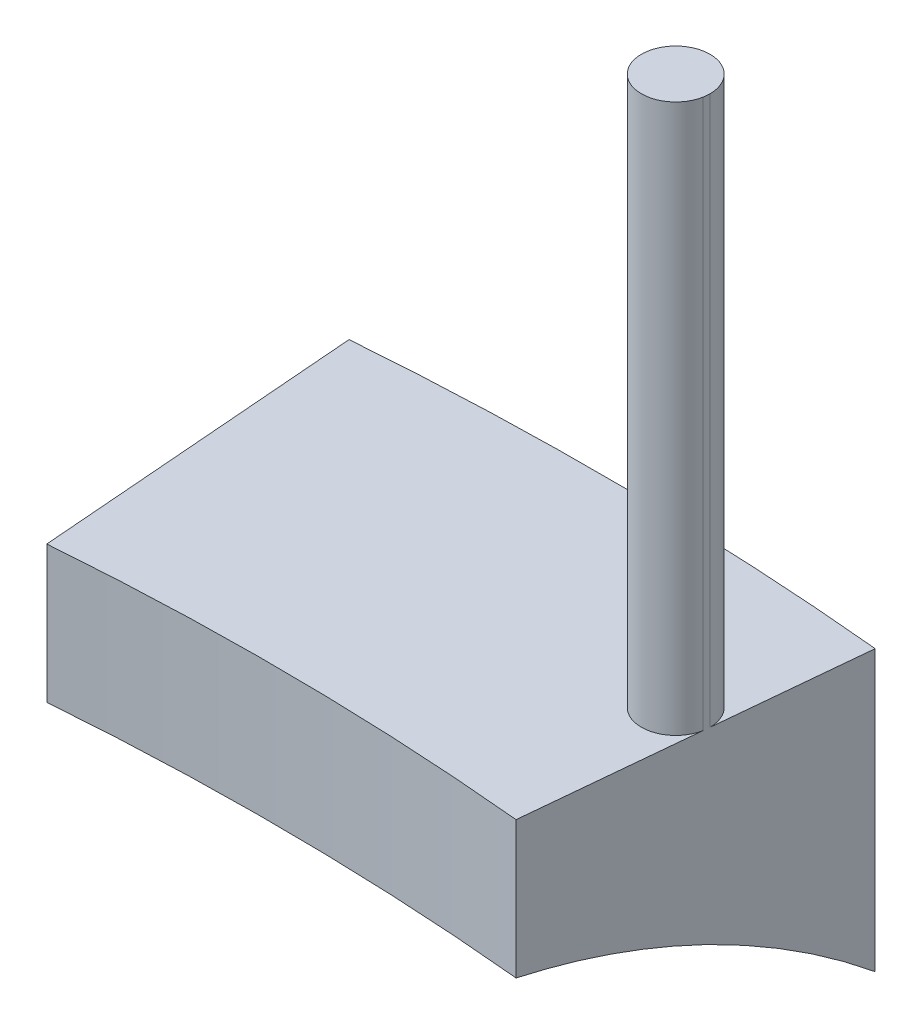
SolidWorks part; units mm, degrees
ref_plane "Front Plane" through (0, 0, 0) normal (0, 0, 1) x (1, 0, 0)
ref_plane "Top Plane" through (0, 0, 0) normal (0, 1, 0) x (1, 0, 0)
ref_plane "Right Plane" through (0, 0, 0) normal (1, 0, 0) x (0, 0, -1)
sketch "Sketch1" plane through (0, 0, 0) normal (0, 1, 0) x (1, 0, 0)
  circle A0 centre (0, 0) radius 140.97
  circle A1 centre (0, 0) radius 125.73
  dimension "D1" = 281.94
  dimension "D2" = 251.46
extrude "Boss-Extrude1" add sketch "Sketch1" along normal blind 12.954
sketch "Sketch3" plane through (0, 12.954, 0) normal (0, 1, 0) x (1, 0, 0)
  line L0 (0, 0) -> (13.4916, 140.3229)
  line L1 (13.4916, 140.3229) -> (0, 0)
  line L2 (0, 0) -> (-11.0802, 140.5339)
  circle A0 centre (0, 0) radius 140.97 construction
  circle A1 centre (0, 0) radius 140.97
  circle M3 centre (0, 0) radius 140.97
  circle M4 centre (0, 0) radius 125.73
  dimension "D1" = 10
extrude "Cut-Extrude1" cut sketch "Sketch3" against normal blind 12.954 contours L0 L2 M4 | L2 L0 M4 M3 region at (-0.0205, 12.954, 2.3917) region at (16.7282, 12.954, -132.3566)
sketch "Sketch5" plane through (0, 0, 0) normal (0, 1, 0) x (1, 0, 0)
  line L0 (-9.8823, 125.341) -> (-11.0802, 140.5339) construction
  line L1 (12.033, 125.1529) -> (13.4916, 140.3229) construction
  arc A1 (-10.4813, 132.9374) -> (12.7623, 132.7379) centre (0, 0) cw
  circle A2 centre (11.2323, 133.3451) radius 1.5875
  dimension "D1" = 3.175
  dimension "D2" = 1.53
  dimension "D3" = 133.35
extrude "Boss-Extrude2" add sketch "Sketch5" along normal blind 38.354 contours A2
sketch "Sketch2" plane through (0, 0, 0) normal (0, 0, 1) x (1, 0, 0)
  line L0 (0, 12.954) -> (-125.73, 12.954)
  line L1 (13.4916, 12.954) -> (-11.0802, 12.954) construction
  line L2 (-125.73, 12.954) -> (-125.73, 6.604)
  line L3 (-125.73, 6.604) -> (-125.73, 0)
  line L4 (-125.73, 0) -> (-140.97, 0)
  line L5 (0, 0) -> (0, 30.8515)
  arc A0 (-125.73, 6.604) -> (-140.97, 0) centre (-121.1655, -24.8162) ccw
  dimension "D3" = 31.75
  dimension "D1" = 125.73
  dimension "D2" = 6.35
revolve "Cut-Revolve1" cut sketch "Sketch2" angle 360 about L5
sketch "Sketch6" plane through (0, 0, 0) normal (0.9954, 0, 0.0957) x (0.0957, 0, -0.9954)
  line L1 (114.9487, -1.4366) -> (150.8904, -1.4366)
  line L2 (114.9487, -1.4366) -> (114.9487, 48.5634)
  line L3 (114.9487, 48.5634) -> (150.8904, 48.5634)
  line L4 (150.8904, -1.4366) -> (150.8904, 48.5634)
  dimension "D1" = 50
extrude "Cut-Extrude2" cut sketch "Sketch6" along normal blind 25.4
